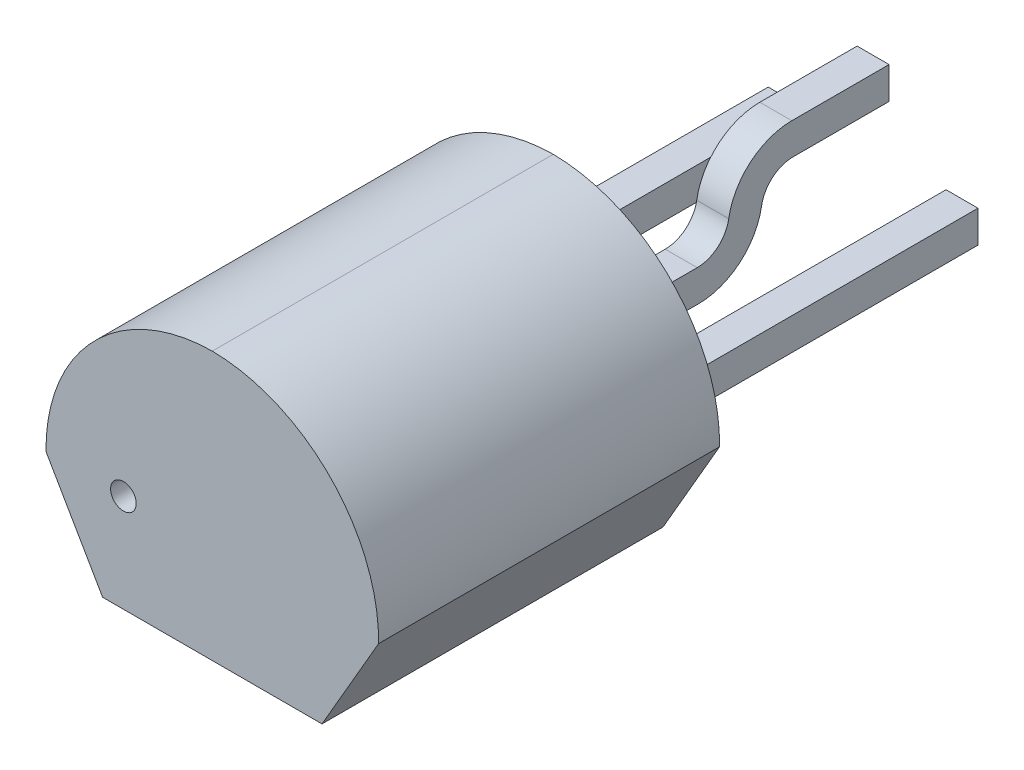
SolidWorks part; units mm, degrees
ref_plane "Спереди" through (0, 0, 0) normal (0, 0, 1) x (1, 0, 0)
ref_plane "Сверху" through (0, 0, 0) normal (0, 1, 0) x (1, 0, 0)
ref_plane "Справа" through (0, 0, 0) normal (1, 0, 0) x (0, 0, -1)
sketch "Эскиз1" plane through (0, 0, 0) normal (0, 0, 1) x (1, 0, 0)
  line L0 (1.14, 0.25) -> (1.64, 0.25)
  line L1 (-0.25, 0.25) -> (0.25, 0.25)
  line L2 (-0.25, 0.25) -> (-0.25, -0.25)
  line L3 (-0.25, -0.25) -> (0.25, -0.25)
  line L4 (0.25, 0.25) -> (0.25, -0.25)
  line L5 (1.14, 0.25) -> (1.14, -0.25)
  line L6 (1.14, -0.25) -> (1.64, -0.25)
  line L7 (1.64, 0.25) -> (1.64, -0.25)
  line L8 (2.53, 0.25) -> (3.03, 0.25)
  line L9 (2.53, 0.25) -> (2.53, -0.25)
  line L10 (2.53, -0.25) -> (3.03, -0.25)
  line L11 (3.03, 0.25) -> (3.03, -0.25)
  line L12 (1.39, 0.25) -> (1.39, -1.8309) construction
  dimension "D1" = 0.5
  dimension "D2" = 0.5
  dimension "D3" = 1.39
ref_plane "Плоскость1" through (0, 0, 2.54) normal (0, 0, 1) x (1, 0, 0)
sketch "Эскиз3" plane through (0, 0, 2.54) normal (0, 0, 1) x (1, 0, 0)
  line L0 (-0.325, -1.53) -> (3.105, -1.53)
  line L6 (-1.21, 0) -> (-0.325, -1.53)
  line L7 (3.99, 0) -> (3.105, -1.53)
  arc A0 (-1.21, 0) -> (1.39, 2.66) centre (1.42, 0.03) cw
  arc A1 (1.39, 2.66) -> (3.99, 0) centre (1.36, 0.03) cw
  dimension "D3" = 2.6302
  dimension "D4" = 2.6302
  dimension "D1" = 5.2
  dimension "D2" = 4.19
  dimension "D5" = 3.43
  dimension "D6" = 1.21
  dimension "D7" = 120.046
extrude "Вытянуть1" add sketch "Эскиз3" along normal blind 5.33
extrude "Вытянуть2" add sketch "Эскиз1" along normal blind 2.54
extrude "Вытянуть3" add sketch "Эскиз1<2>" against normal blind 10.16
sketch "Эскиз1<2>" plane through (0, 0, 0) normal (0, 0, 1) x (1, 0, 0) same geometry as "Эскиз1"
sketch "Эскиз4" plane through (0, 0, 7.87) normal (0, 0, 1) x (1, 0, 0)
  circle A0 centre (0, 0) radius 0.2
extrude "Вырез-Вытянуть1" cut sketch "Эскиз4" against normal blind 0.5
sketch "Эскиз5" plane through (0, 0.25, 0) normal (0, 1, 0) x (1, 0, 0)
  line L0 (1.14, -0.04) -> (1.64, -0.04)
  line L4 (1.64, -2.54) -> (1.64, 10.16)
  line L5 (1.64, 10.16) -> (1.14, 10.16)
  line L6 (1.14, 10.16) -> (1.14, -2.54)
  line L7 (1.14, -2.54) -> (1.64, -2.54)
  line L8 (1.64, -0.04) -> (1.64, 10.16)
  line L9 (1.64, 10.16) -> (1.14, 10.16)
  line L10 (1.14, 10.16) -> (1.14, -0.04)
  dimension "D1" = 0
extrude "Вытянуть4" add sketch "Эскиз5" along normal blind 1.25
sketch "Эскиз6" plane through (1.64, 0, 0) normal (1, 0, 0) x (0, 0, -1)
  line L0 (-0.04, 1.5) -> (10.16, 1.5) construction
  line L1 (2.46, -0.8385) -> (10.7871, -0.8385)
  line L2 (2.46, 1) -> (2.46, 2.2869)
  line L3 (0.96, 1) -> (2.46, 1)
  line L4 (10.7871, -0.8385) -> (10.7871, 1)
  line L6 (0.46, 0.5) -> (2.46, 0.5)
  line L7 (2.46, 0.5) -> (2.46, -0.8385)
  line L8 (2.46, 2.2869) -> (10.7871, 2.2869)
  line L9 (10.7871, 2.2869) -> (10.7871, 1)
  arc A0 (0.46, 0.5) -> (0.96, 1) centre (0.96, 0.5) cw
  dimension "D3" = 0.5
  dimension "D1" = 0.5
  dimension "D2" = 2
extrude "Вырез-Вытянуть2" cut sketch "Эскиз6" against normal blind 10 and the other way blind 10
fillet "Скругление1" radius 0.5 1 edges at (1.39, 0.25, 0.04)
fillet "Скругление2" radius 1 1 edges at (1.39, 1.5, 0.04)
sketch "Эскиз7" plane through (0, 0, -2.46) normal (0, 0, -1) x (-1, 0, 0)
  line L4 (-1.14, -0.25) -> (-1.14, 0.5)
  line L5 (-1.14, 0.5) -> (-1.64, 0.5)
  line L6 (-1.64, 0.5) -> (-1.64, -0.25)
  line L7 (-1.64, -0.25) -> (-1.14, -0.25)
  line L8 (-1.14, -0.25) -> (-1.14, 0.5)
  line L9 (-1.14, 0.5) -> (-1.64, 0.5)
  line L10 (-1.64, 0.5) -> (-1.64, -0.25)
  line L11 (-1.64, -0.25) -> (-1.14, -0.25)
  dimension "D1" = 0
extrude "Вырез-Вытянуть3" cut sketch "Эскиз7" against normal blind 2
fillet "Скругление3" radius 1 1 edges at (1.39, -0.25, -0.46)
